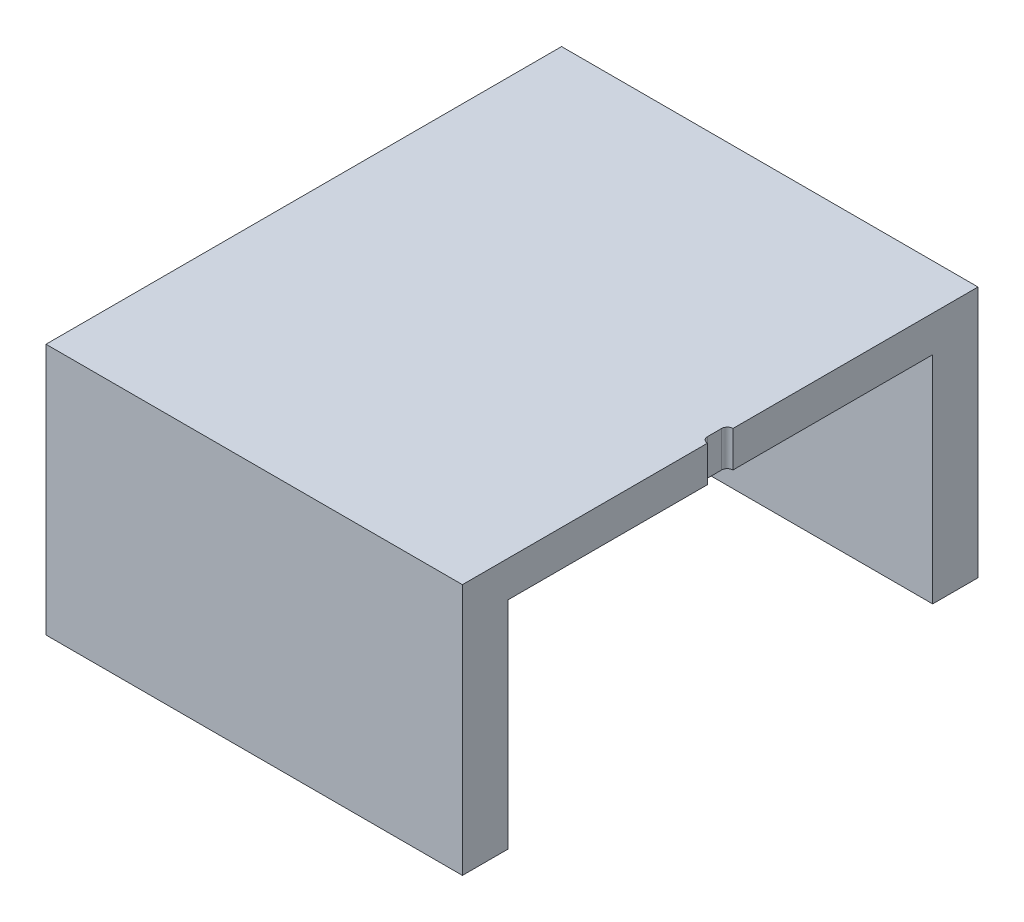
SolidWorks part; units mm, degrees
material "6061 Alloy"
ref_plane "Front Plane" through (0, 0, 0) normal (0, 0, 1) x (1, 0, 0)
ref_plane "Top Plane" through (0, 0, 0) normal (0, 1, 0) x (1, 0, 0)
ref_plane "Right Plane" through (0, 0, 0) normal (1, 0, 0) x (0, 0, -1)
sketch "MainSketch" plane through (0, 0, 0) normal (0, 1, 0) x (1, 0, 0)
  line L0 (0, -4) -> (-32.75, -4)
  line L1 (0, 0) -> (-36.75, 0)
  line L2 (0, 0) -> (0, -45.5)
  line L3 (0, -45.5) -> (-36.75, -45.5)
  line L4 (-36.75, 0) -> (-36.75, -45.5)
  line L5 (-32.75, -4) -> (-32.75, -41.5)
  line L6 (-32.75, -41.5) -> (0, -41.5)
  line L7 (31.75, -5) -> (-31.75, -5) construction
  line L8 (-31.75, -5) -> (-31.75, -40.5) construction
  line L9 (-31.75, -40.5) -> (31.75, -40.5) construction
  line L10 (0, -22.125) -> (0, -23.375) construction
  line L11 (0.5, -22.125) -> (0.5, -23.375)
  line L12 (-0.5, -22.125) -> (-0.5, -23.375)
  arc A0 (0.5, -22.125) -> (-0.5, -22.125) centre (0, -22.125) ccw
  arc A1 (-0.5, -23.375) -> (0.5, -23.375) centre (0, -23.375) ccw
  point P7 (-10, -2.5)
  point P10 (-34.25, -2.5)
  point P11 (-34.25, -43)
  point P12 (-10, -43)
  point P17 (0, -22.75)
  dimension "D14" = 0.5
  dimension "D1" = 4
  dimension "D2" = 4
  dimension "D3" = 4
  dimension "D4" = 36.75
  dimension "D6" = 5
  dimension "D7" = 5
  dimension "D8" = 5
  dimension "D9" = 2.5
  dimension "D10" = 2.5
  dimension "D11" = 10
  dimension "D12" = 10
  dimension "D13" = 2.5
  dimension "D15" = 1.25
  dimension "D5" = 35.5
  dimension "D16" = 63.5
extrude "Wall" add sketch "MainSketch" along normal blind 19.05 contours L6 L5 L0 L2 L1 L4 L3 region at (-16.375, 0, 3.4151)
extrude "Roof" add sketch "MainSketch<3>" along normal blind 3.175 from surface contours L5 L6 L2 L0 | L6 L5 L0 L2 L1 L4 L3 region at (-16.3884, 0, 22.75) region at (-16.375, 0, 3.4151) starting at face at (-17.375, 19.05, 22.75)
sketch "MainSketch<3>" plane through (0, 0, 0) normal (0, 1, 0) x (1, 0, 0) same geometry as "MainSketch"
hole_wizard "#2-56 Tapped Hole1" positions "3DSketch1" profile "Sketch2" tap size "#2-56" standard "ANSI Inch"
sketch3d "3DSketch1"
  point P0 (-10, 0, 43)
  point P2 (-34.25, 0, 43)
  point P4 (-34.25, 0, 2.5)
  point P6 (-10, 0, 2.5)
sketch "Sketch2" plane through (-10, 0, 43) normal (1, 0, 0) x (0, 0, -1)
  line L0 (0, 0) -> (0, 6.2642)
  line L1 (0, 6.2642) -> (0.889, 5.73)
  line L2 (0.889, 5.73) -> (0.889, 0)
  line L5 (0.889, 0) -> (0, 0)
  line L10 (0, 6.2642) -> (-0.889, 5.73) construction
  line L11 (0, -6.35) -> (0, 107.95) construction
  dimension "Tap Drill Dia." = 1.778
  dimension "Tap Drill Depth" = 5.73
  dimension "Drill Angle" = 118
cosmetic thread "Hole Thread1" parameters "D1"=4.37, "D2"=2.1844
cosmetic thread "Hole Thread2" parameters "D1"=4.37, "D2"=2.1844
cosmetic thread "Hole Thread3" parameters "D1"=4.37, "D2"=2.1844
cosmetic thread "Hole Thread4" parameters "D1"=4.37, "D2"=2.1844
equation "\"D2@MainSketch\" = \"D1@MainSketch\""
equation "\"D3@MainSketch\" = \"D2@MainSketch\""
equation "\"D7@MainSketch\" = \"D6@MainSketch\""
equation "\"D8@MainSketch\" = \"D6@MainSketch\""
equation "\"D9@MainSketch\" = \"D7@MainSketch\" / 2"
equation "\"D10@MainSketch\" = \"D9@MainSketch\""
equation "\"D12@MainSketch\" = \"D11@MainSketch\""
equation "\"D13@MainSketch\" = \"D10@MainSketch\""
equation "\"D4@MainSketch\"=(\"D16@MainSketch\"+\"D6@MainSketch\"*2)/2"
